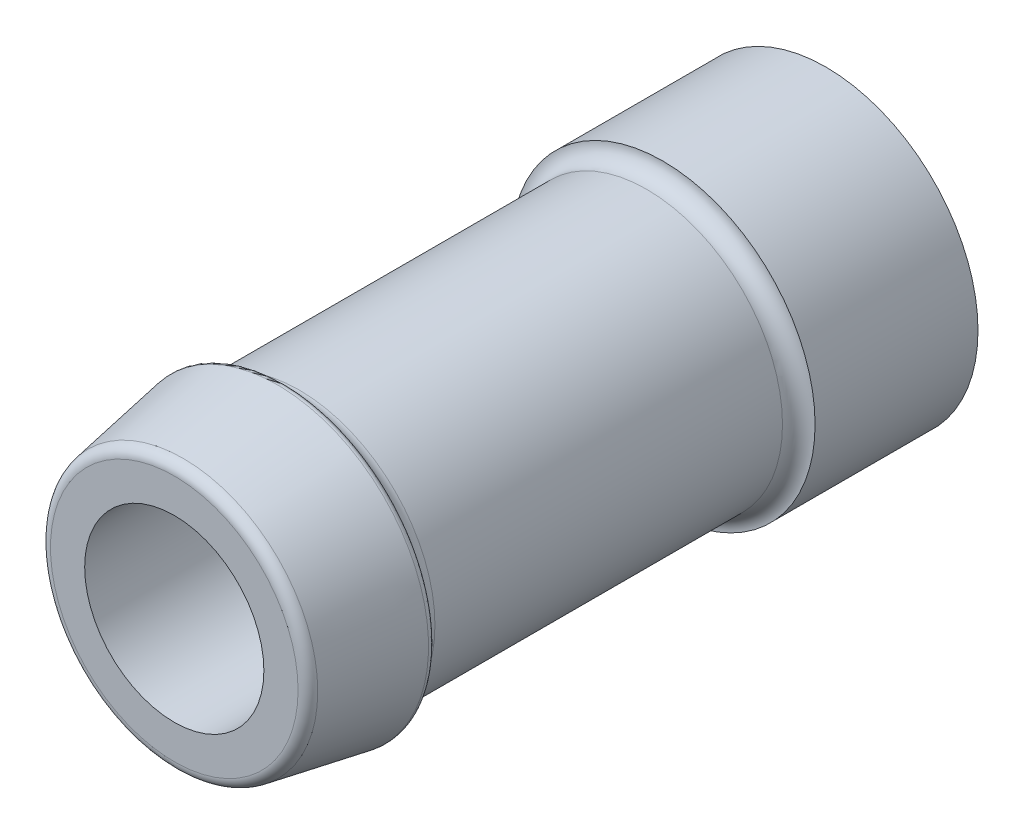
SolidWorks part; units mm, degrees
material "Custom Plastic"
ref_plane "X-Y Datum" through (0, 0, 0) normal (0, 0, 1) x (1, 0, 0)
ref_plane "X-Z Datum" through (0, 0, 0) normal (0, 1, 0) x (1, 0, 0)
ref_plane "Y-Z Datum" through (0, 0, 0) normal (1, 0, 0) x (0, 0, -1)
sketch "Sketch1" plane through (0, 0, 0) normal (0, 0, 1) x (1, 0, 0)
  circle A0 centre (0, 0) radius 7.112
  dimension "D1" = 14.224
extrude "Boss-Extrude1" add sketch "Sketch1" along normal blind 30.48
sketch "Sketch2" plane through (0, 0, 30.48) normal (0, 0, 1) x (1, 0, 0)
  circle A0 centre (0, 0) radius 4.191
  dimension "D1" = 8.382
extrude "Cut-Extrude1" cut sketch "Sketch2" against normal blind 30.48
sketch "Sketch3" plane through (0, 0, 30.48) normal (0, 0, 1) x (1, 0, 0)
  circle A0 centre (0, 0) radius 6.35
  circle A1 centre (0, 0) radius 7.874
  dimension "D1" = 12.7
  dimension "D2" = 15.748
extrude "Cut-Extrude2" cut sketch "Sketch3" against normal blind 17.78 from offset 5.08 offset against normal yes
fillet "Fillet1" radius 0.762 1 edges at (6.35, 0, 7.62)
fillet "Fillet2" radius 0.762 1 edges at (6.35, 0, 25.4)
chamfer "Chamfer1" distance 5.08 angle 10 1 edges at (7.112, 0, 30.48) first distance on face at (7.112, 0, 25.4)
fillet "Fillet3" radius 0.508 1 edges at (6.2163, 0, 30.48)
fillet "Fillet4" radius 0.254 1 edges at (7.112, 0, 25.4)
